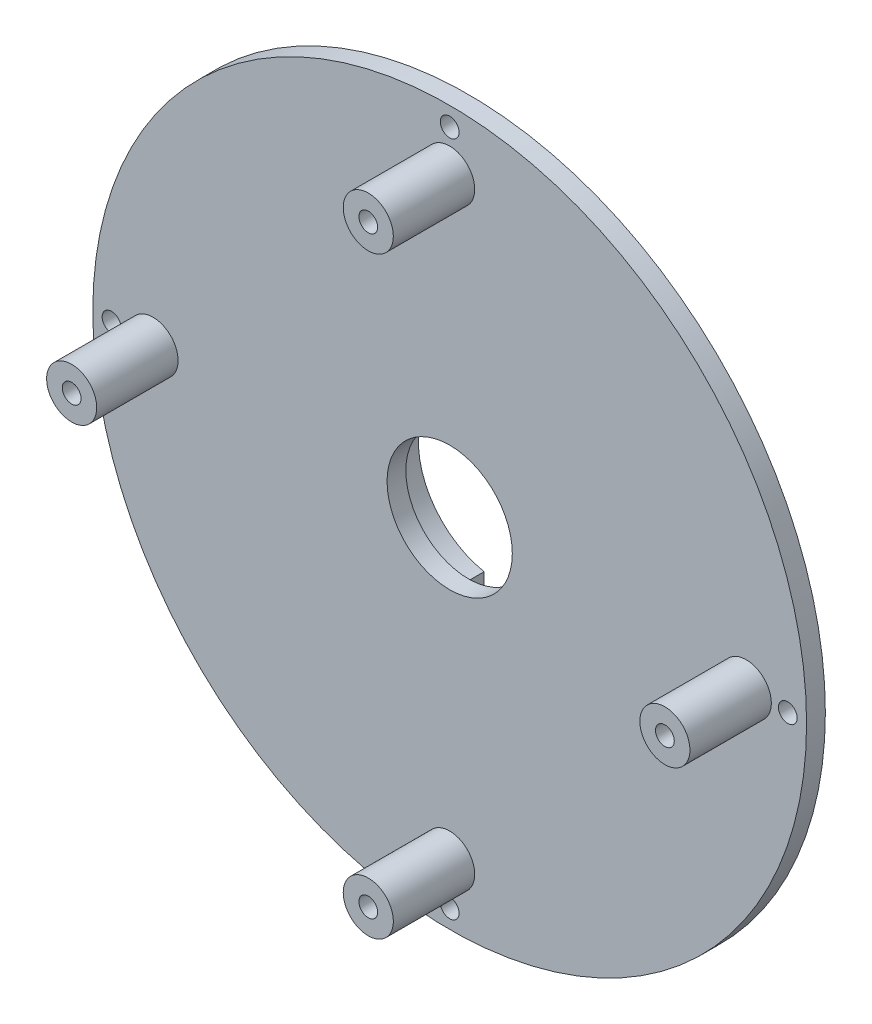
SolidWorks part; units mm, degrees
ref_plane "Front Plane" through (0, 0, 0) normal (0, 0, 1) x (1, 0, 0)
ref_plane "Top Plane" through (0, 0, 0) normal (0, 1, 0) x (1, 0, 0)
ref_plane "Right Plane" through (0, 0, 0) normal (1, 0, 0) x (0, 0, -1)
sketch "Sketch1" plane through (0, 0, 0) normal (0, 0, 1) x (1, 0, 0)
  circle A0 centre (0, 0) radius 57
  dimension "D1" = 114
extrude "Boss-Extrude1" add sketch "Sketch1" along normal blind 3
sketch "Sketch2" plane through (0, 0, 0) normal (0, 0, -1) x (-1, 0, 0)
  circle A0 centre (0, 0) radius 15
  dimension "D1" = 30
extrude "Boss-Extrude2" add sketch "Sketch2" along normal blind 5
sketch "Sketch3" plane through (0, 0, -5) normal (0, 0, -1) x (-1, 0, 0)
  circle A0 centre (0, 0) radius 13
  dimension "D1" = 26
extrude "Cut-Extrude1" cut sketch "Sketch3" against normal up to surface (5 mm away) up to face at (-15, 0, 0)
sketch "Sketch4" plane through (0, 0, 0) normal (0, 0, -1) x (-1, 0, 0)
  circle A0 centre (0, 0) radius 10
  dimension "D1" = 20
extrude "Cut-Extrude2" cut sketch "Sketch4" against normal up to surface (3 mm away) up to face at (57, 0, 3)
ref_plane "Plane1" through (0, 0, -5) normal (0, 0, -1) x (-1, 0, 0)
sketch "Sketch6" plane through (0, 0, -5) normal (0, 0, -1) x (-1, 0, 0)
  line L1 (-2.5, -25) -> (2.5, -25)
  line L2 (-2.5, -25) -> (-2.5, 25)
  line L3 (-2.5, 25) -> (2.5, 25)
  line L4 (2.5, -25) -> (2.5, 25)
  line L5 (-2.5, -25) -> (2.5, 25) construction
  line L6 (-2.5, 25) -> (2.5, -25) construction
  point P0 (0, 0)
  dimension "D1" = 50
  dimension "D2" = 5
extrude "Cut-Extrude4" cut sketch "Sketch6" against normal up to surface (5 mm away) up to face at (-15, 0, 0)
sketch "Sketch7" plane through (0, 0, 0) normal (0, 0, -1) x (-1, 0, 0)
  circle A0 centre (0, 0) radius 54
  dimension "D1" = 108
sketch "Sketch8" plane through (0, 0, 0) normal (0, 0, -1) x (-1, 0, 0)
  circle A0 centre (0, 54) radius 1.5
  circle A1 centre (0, 0) radius 54 construction
  circle A2 centre (54, 0) radius 1.5
  circle A3 centre (0, -54) radius 1.5
  circle A4 centre (-54, 0) radius 1.5
  point P6 (0, 0)
  dimension "D1" = 3
  dimension "D2" = 4
extrude "Cut-Extrude5" cut sketch "Sketch8" against normal up to surface (3 mm away) up to face at (10, 0, 3)
sketch "Sketch9" plane through (0, 0, 3) normal (0, 0, 1) x (1, 0, 0)
  circle A0 centre (0, 47.37) radius 4
  dimension "D2" = 8
  dimension "D1" = 47.37
extrude "Boss-Extrude4" add sketch "Sketch9" along normal blind 13
sketch "Sketch11" plane through (0, 0, 16) normal (0, 0, 1) x (1, 0, 0)
  circle A0 centre (0, 47.37) radius 1.5
  dimension "D1" = 3
extrude "Cut-Extrude6" cut sketch "Sketch11" against normal up to surface (13 mm away) up to face at (4, 47.37, 3)
ref_axis "Axis1" through (0, 0, -6) along (0, 0, 1)
pattern_circular "CirPattern1" count 4 over 360 about axis through (0, 0, -6) along (0, 0, 1) of "Boss-Extrude4", "Cut-Extrude6"
